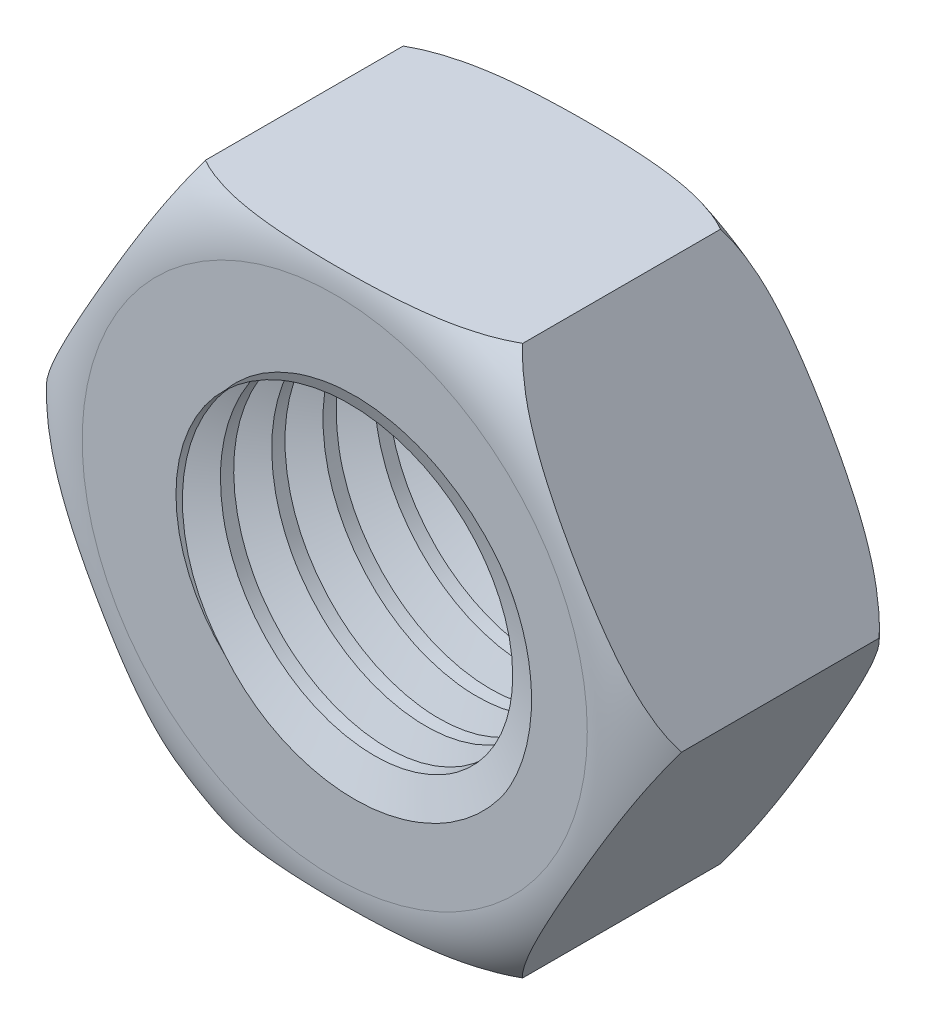
SolidWorks part; units mm, degrees
ref_plane "Front Plane" through (0, 0, 0) normal (0, 0, 1) x (1, 0, 0)
ref_plane "Top Plane" through (0, 0, 0) normal (0, 1, 0) x (1, 0, 0)
ref_plane "Right Plane" through (0, 0, 0) normal (1, 0, 0) x (0, 0, -1)
sketch "Sketch1" plane through (0, 0, 0) normal (0, 0, 1) x (1, 0, 0)
  line L1 (-16.4978, 0) -> (-8.2489, -14.2875)
  line L2 (-8.2489, -14.2875) -> (8.2489, -14.2875)
  line L3 (8.2489, -14.2875) -> (16.4978, 0)
  line L4 (16.4978, 0) -> (8.2489, 14.2875)
  line L5 (8.2489, 14.2875) -> (-8.2489, 14.2875)
  line L6 (-8.2489, 14.2875) -> (-16.4978, 0)
  circle A0 centre (0, 0) radius 14.2875 construction
  dimension "D1" = 28.575
extrude "Boss-Extrude1" add sketch "Sketch1" along normal mid plane 13.335
sketch "Sketch4" plane through (0, 0, 0) normal (0, 1, 0) x (1, 0, 0)
  line L0 (-13.1318, 6.6675) -> (-16.4978, 6.6675)
  line L1 (-16.4978, 6.6675) -> (-16.4978, 5.1435)
  line L2 (-16.4978, -6.6675) -> (-16.4978, 6.6675) construction
  line L3 (-8.2489, 6.6675) -> (-16.4978, 6.6675) construction
  line L4 (8.2489, -6.6675) -> (-8.2489, -6.6675) construction
  line L5 (0, -6.6675) -> (0, 6.6675) construction
  line L6 (8.2489, 6.6675) -> (-8.2489, 6.6675) construction
  arc A0 (-13.1318, 6.6675) -> (-16.4978, 5.1435) centre (-13.1318, 2.1884) ccw
  point P5 (0, -6.6675)
  point P13 (0, -6.6675)
  dimension "D1" = 1.524
  dimension "D2" = 26.2636
revolve "Cut-Revolve1" cut sketch "Sketch4" angle 360 about L5
mirror "Mirror2" about plane through (0, 0, 0) normal (0, 0, 1) of "Cut-Revolve1"
sketch "Sketch6" plane through (0, 0, 0) normal (0, 0, 1) x (1, 0, 0)
  circle A0 centre (0, 0) radius 8.255
  dimension "D1" = 16.51
extrude "Cut-Extrude2" cut sketch "Sketch6" against normal mid plane 13.335 contours A0
ref_plane "Plane2" through (0, 0, 9.3345) normal (0, 0, 1) x (1, 0, 0)
sketch "Sketch8" plane through (0, 0, 9.3345) normal (0, 0, 1) x (1, 0, 0)
  circle A0 centre (0, 0) radius 8.255 construction
  circle A1 centre (0, 0) radius 8.255
curve "Helix/Spiral1" pitch 2.667 height 21.336 radius 8.255 centre (0, 0, 9.3345) axis (0, 0, -1) start towards (1, 0, 0)
sketch "Sketch10" plane through (0, 0, 0) normal (0, 1, 0) x (1, 0, 0)
  line L0 (8.255, -9.3345) -> (13.0713, -9.3345) construction
  line L1 (8.255, -10.3235) -> (8.255, -8.3455)
  line L2 (8.255, -8.3455) -> (10.0761, -9.0998)
  line L3 (8.255, -10.3235) -> (10.0761, -9.5692)
  arc A0 (10.0761, -9.0998) -> (10.0761, -9.5692) centre (9.9789, -9.3345) cw
  point P7 (10.6426, -9.3345)
  dimension "D2" = 0.254
  dimension "D1" = 2.3876
  dimension "D3" = 45
sweep "Cut-Sweep1" cut profiles "Sketch10" path "Helix/Spiral1"
